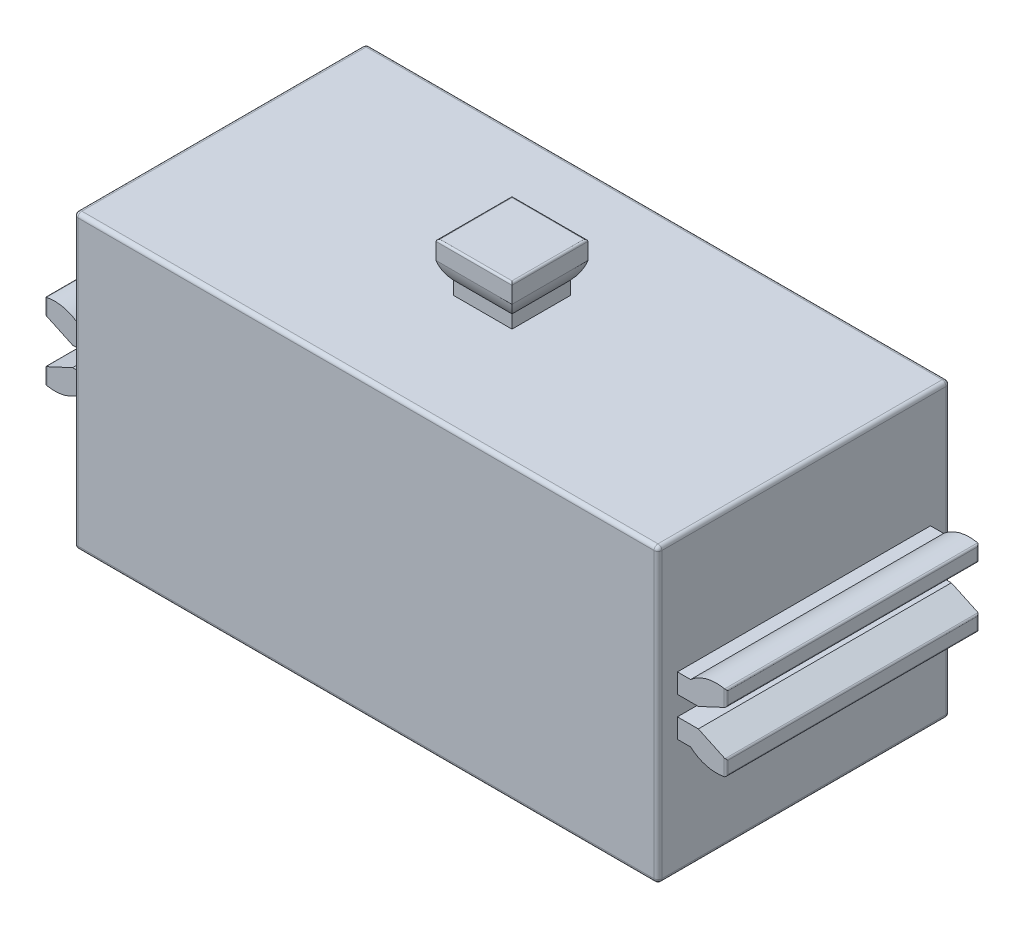
SolidWorks part; units mm, degrees
ref_plane "前视基准面" through (0, 0, 0) normal (0, 0, 1) x (1, 0, 0)
ref_plane "上视基准面" through (0, 0, 0) normal (0, 1, 0) x (1, 0, 0)
ref_plane "右视基准面" through (0, 0, 0) normal (1, 0, 0) x (0, 0, -1)
sketch "草图1" plane through (0, 0, 0) normal (0, 0, 1) x (1, 0, 0)
  line L1 (-15, -7.5) -> (15, -7.5)
  line L2 (-15, -7.5) -> (-15, 7.5)
  line L3 (-15, 7.5) -> (15, 7.5)
  line L4 (15, -7.5) -> (15, 7.5)
extrude "凸台-拉伸1" add sketch "草图1" along normal blind 7.5 and the other way blind 7.5
sketch "草图2" plane through (0, 0, 7.5) normal (0, 0, 1) x (1, 0, 0)
  line L0 (-15, 7.5) -> (-15, -7.5) construction
  line L1 (-15.6771, 1.5) -> (-15, 1.5)
  line L2 (-17.5, 1.9365) -> (-17.5, 1.1658)
  line L3 (-15.6771, -1.5) -> (-15, -1.5)
  line L4 (-15, 1.5) -> (-15, 0.5)
  line L5 (-16.0723, 0.5) -> (-17.5, 1.1658)
  line L6 (-16.0723, -0.5) -> (-17.5, -1.1658)
  line L7 (-17.5, -1.1658) -> (-17.5, -1.9365)
  line L8 (-15, -0.5) -> (-16.0723, -0.5)
  line L9 (0, 8.7474) -> (0, -8.6547) construction
  line L10 (-15, 0.5) -> (-16.0723, 0.5)
  line L11 (-15, -0.5) -> (-15, -1.5)
  line L12 (15, -0.5) -> (15, -1.5)
  line L13 (15, 0.5) -> (16.0723, 0.5)
  line L14 (15, -0.5) -> (16.0723, -0.5)
  line L15 (17.5, -1.1658) -> (17.5, -1.9365)
  line L16 (16.0723, -0.5) -> (17.5, -1.1658)
  line L17 (16.0723, 0.5) -> (17.5, 1.1658)
  line L18 (15, 1.5) -> (15, 0.5)
  line L19 (15.6771, -1.5) -> (15, -1.5)
  line L20 (17.5, 1.9365) -> (17.5, 1.1658)
  line L21 (15.6771, 1.5) -> (15, 1.5)
  arc A0 (-15.6771, 1.5) -> (-17.5, 1.9365) centre (-17, 0) ccw
  arc A1 (-17.5, -1.9365) -> (-15.6771, -1.5) centre (-17, 0) ccw
  arc A2 (17.5, -1.9365) -> (15.6771, -1.5) centre (17, 0) cw
  arc A3 (15.6771, 1.5) -> (17.5, 1.9365) centre (17, 0) cw
extrude "凸台-拉伸2" add sketch "草图2" against normal blind 13 from offset 1 offset against normal yes
sketch "草图3" plane through (0, 7.5, 0) normal (0, 1, 0) x (-1, 0, 0)
  line L1 (1.5, -1.5) -> (-1.5, -1.5)
  line L2 (1.5, -1.5) -> (1.5, 1.5)
  line L3 (1.5, 1.5) -> (-1.5, 1.5)
  line L4 (-1.5, -1.5) -> (-1.5, 1.5)
extrude "凸台-拉伸3" add sketch "草图3" along normal blind 1
sketch "草图4" plane through (0, 0, 0) normal (0, 0, 1) x (1, 0, 0)
  line L0 (-1.95, 10) -> (1.95, 10)
  line L1 (-1.95, 10) -> (-1.95, 9.0556)
  line L2 (1.95, 10) -> (1.95, 9.0556)
  line L5 (-1.5, 8.1771) -> (1.5, 8.1771)
  line L6 (1.5, 8.5) -> (1.5, 7.5) construction
  arc A0 (1.5, 8.1771) -> (1.95, 9.0556) centre (0, 9.5) ccw
  arc A2 (-1.95, 9.0556) -> (-1.5, 8.1771) centre (0, 9.5) ccw
extrude "凸台-拉伸4" add sketch "草图4" along normal blind 2 and the other way blind 3
sketch "草图5" plane through (1.95, 0, 0) normal (1, 0, 0) x (0, 0, -1)
  line L1 (-1.95, 10) -> (-1.95, 9.0556)
  line L2 (-2, 10) -> (-1.95, 10)
  line L3 (-2, 10) -> (-2, 8.1771)
  line L4 (-2, 8.1771) -> (-1.5, 8.1771)
  line L5 (3, 10) -> (3, 8.1771)
  line L6 (1.95, 10) -> (1.95, 9.0556)
  line L7 (1.95, 10) -> (3, 10)
  line L8 (1.5, 8.1771) -> (3, 8.1771)
  arc A0 (1.5, 8.1771) -> (1.95, 9.0556) centre (0, 9.5) ccw
  arc A1 (-1.95, 9.0556) -> (-1.5, 8.1771) centre (0, 9.5) ccw
extrude "切除-拉伸1" cut sketch "草图5" against normal up to next
sketch "草图6" plane through (0, -7.5, 0) normal (0, -1, 0) x (1, 0, 0)
  circle A0 centre (-5, 4) radius 2.25
  circle A1 centre (5, 4) radius 2.25
extrude "切除-拉伸2" cut sketch "草图6" against normal blind 2
sketch "草图7" plane through (0, -7.5, 0) normal (0, -1, 0) x (1, 0, 0)
  line L1 (-5, 6) -> (-5, 2)
  arc A0 (-5, 2) -> (-5, 6) centre (-5, 4) ccw
revolve "旋转1" add sketch "草图7" angle 360 about L1
sketch "草图8" plane through (0, -7.5, 0) normal (0, -1, 0) x (1, 0, 0)
  line L0 (5, 6) -> (5, 2)
  arc A0 (5, 2) -> (5, 6) centre (5, 4) ccw
revolve "旋转2" add sketch "草图8" angle 360 about L0
sketch "草图10" plane through (0, -7.5, 0) normal (0, -1, 0) x (1, 0, 0)
  line L0 (0, 1.6062) -> (0, -8.6447) construction
  line L1 (-6.75, -2) -> (-3.25, -2)
  line L2 (-6.75, -2) -> (-6.75, -5.7932)
  line L3 (-6.75, -5.7932) -> (-3.25, -5.7932)
  line L4 (-3.25, -2) -> (-3.25, -5.7932)
  line L5 (3.25, -2) -> (3.25, -5.7932)
  line L6 (6.75, -5.7932) -> (3.25, -5.7932)
  line L7 (6.75, -2) -> (6.75, -5.7932)
  line L8 (6.75, -2) -> (3.25, -2)
extrude "切除-拉伸3" cut sketch "草图10" against normal blind 1
sketch "草图11" plane through (0, -6.5, 0) normal (0, -1, 0) x (1, 0, 0)
  line L0 (-5, -3.25) -> (-5, -4.75)
  arc A0 (-5, -4.75) -> (-5, -3.25) centre (-5, -4) ccw
revolve "旋转3" add sketch "草图11" angle 360 about L0
sketch "草图12" plane through (0, -6.5, 0) normal (0, -1, 0) x (1, 0, 0)
  line L0 (5, -3.25) -> (5, -4.75)
  arc A0 (5, -4.75) -> (5, -3.25) centre (5, -4) ccw
revolve "旋转4" add sketch "草图12" angle 360 about L0
fillet "圆角1" radius 0.1 20 edges at (1.95, 10, 0) (0, 10, 1.95) (-1.95, 10, 0) (0, 10, -1.95) (-17.5, -1.9365, 0) (-17.5, -1.5511, -6.5) (-17.5, -1.1658, 0) (-17.5, -1.5511, 6.5) (-17.5, 1.1658, 0) (-17.5, 1.5511, -6.5) (-17.5, 1.9365, 0) (-17.5, 1.5511, 6.5) (17.5, -1.1658, 0) (17.5, -1.5511, -6.5) (17.5, -1.9365, 0) (17.5, -1.5511, 6.5) (17.5, 1.9365, 0) (17.5, 1.5511, -6.5) (17.5, 1.1658, 0) (17.5, 1.5511, 6.5)
fillet "圆角2" radius 0.2 12 edges at (0, -7.5, -7.5) (15, 0, -7.5) (0, 7.5, -7.5) (-15, 0, -7.5) (0, 7.5, 7.5) (15, 0, 7.5) (0, -7.5, 7.5) (-15, 0, 7.5) (-15, -7.5, 0) (-15, 7.5, 0) (15, 7.5, 0) (15, -7.5, 0)
